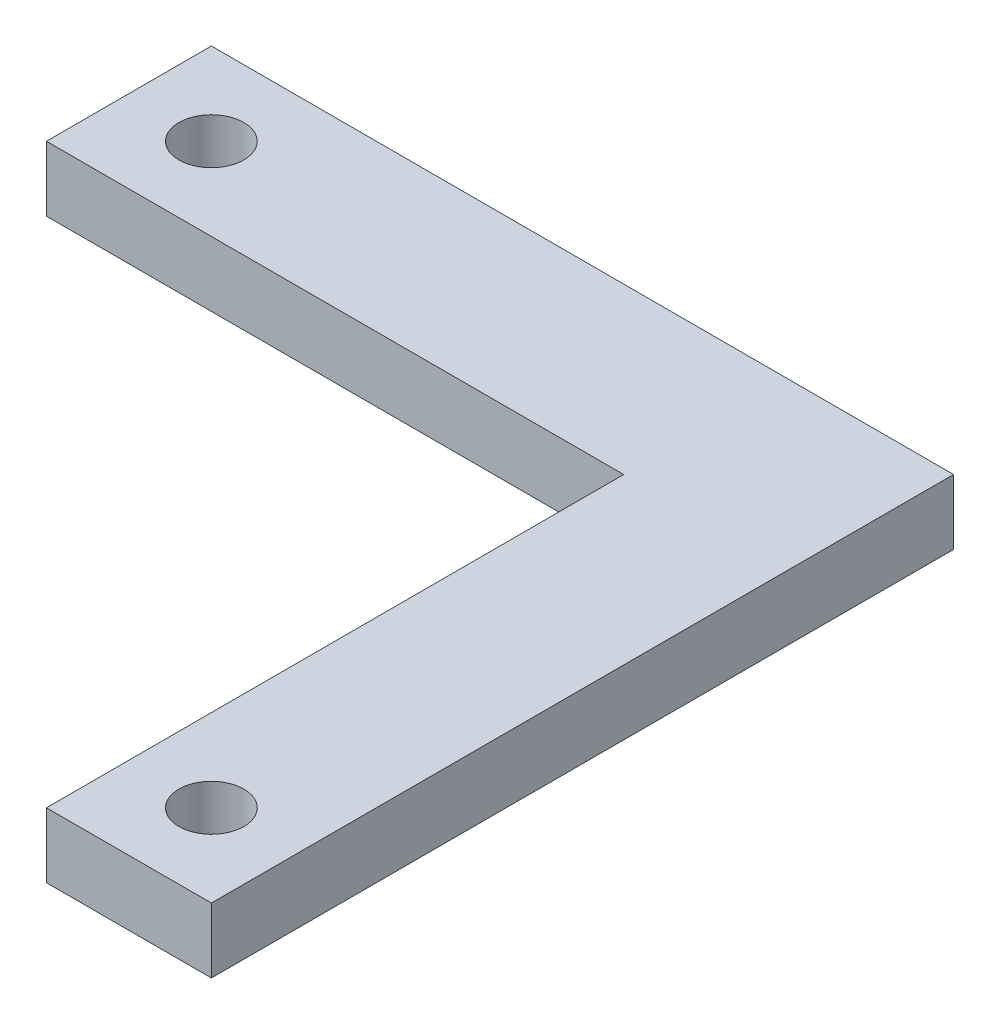
SolidWorks part; units mm, degrees
ref_plane "Front Plane" through (0, 0, 0) normal (0, 0, 1) x (1, 0, 0)
ref_plane "Top Plane" through (0, 0, 0) normal (0, 1, 0) x (1, 0, 0)
ref_plane "Right Plane" through (0, 0, 0) normal (1, 0, 0) x (0, 0, -1)
sketch "Sketch1" plane through (0, 0, 0) normal (0, 1, 0) x (1, 0, 0)
  line L0 (0, 6.35) -> (6.35, 6.35)
  line L2 (0, 0) -> (0, 12.7)
  line L3 (0, 12.7) -> (57.15, 12.7)
  line L4 (57.15, 0) -> (57.15, 12.7)
  line L5 (50.8, -44.45) -> (50.8, -38.1)
  line L7 (44.45, 0) -> (44.45, -44.45)
  line L8 (44.45, -44.45) -> (57.15, -44.45)
  line L9 (57.15, -44.45) -> (57.15, 0)
  line L10 (44.45, 0) -> (0, 0)
  circle A0 centre (6.35, 6.35) radius 2.5
  circle A2 centre (50.8, -38.1) radius 2.5
  dimension "D4" = 5
  dimension "D6" = 6.35
  dimension "D8" = 5
  dimension "D1" = 57.15
  dimension "D2" = 12.7
  dimension "D3" = 6.35
  dimension "D5" = 12.7
  dimension "D7" = 44.45
  dimension "D9" = 12.7
extrude "Boss-Extrude1" add sketch "Sketch1" along normal blind 5 contours L4 L3 L2 A0 region at (0.8082, 0, -9.525)
